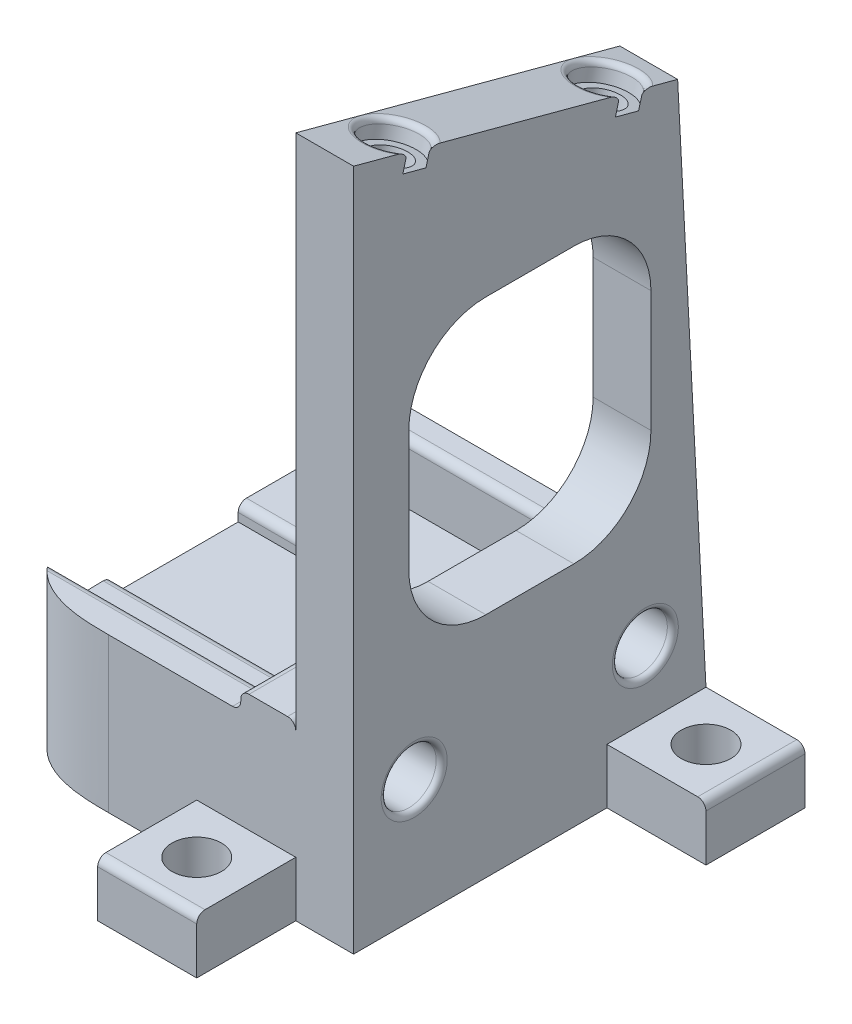
SolidWorks part; units mm, degrees
ref_plane "Front" through (0, 0, 0) normal (0, 0, 1) x (1, 0, 0)
ref_plane "Top" through (0, 0, 0) normal (0, 1, 0) x (1, 0, 0)
ref_plane "Right" through (0, 0, 0) normal (1, 0, 0) x (0, 0, -1)
sketch "Sketch1" plane through (0, 0, 0) normal (1, 0, 0) x (0, 0, -1)
  line L0 (-13.0089, 0) -> (13.0089, 0)
  line L1 (13.0089, 0) -> (13.0089, 8.5)
  line L2 (13.0089, 8.5) -> (5.7589, 8.5)
  line L3 (5.7589, 8.5) -> (5.7589, 7)
  line L4 (5.7589, 7) -> (-5.7589, 7)
  line L5 (-5.7589, 7) -> (-5.7589, 8.5)
  line L6 (-5.7589, 8.5) -> (-13.0089, 8.5)
  line L7 (-13.0089, 8.5) -> (-13.0089, 0)
  dimension "D1" = 8.5
  dimension "D2" = 7.25
  dimension "D3" = 26.0178
  dimension "D4" = 1.5
extrude "Boss-Extrude1" add sketch "Sketch1" along normal mid plane 22
sketch "Sketch3" plane through (0, 0, 0) normal (0, -1, 0) x (1, 0, 0)
  line L1 (-11, -13.0089) -> (11, -13.0089)
  line L2 (-11, -13.0089) -> (-11, -16.0089)
  line L3 (-11, -16.0089) -> (11, -16.0089)
  line L4 (11, -13.0089) -> (11, -16.0089)
  line L5 (-11, 13.0089) -> (11, 13.0089)
  line L6 (-11, 13.0089) -> (-11, 16.0089)
  line L7 (-11, 16.0089) -> (11, 16.0089)
  line L8 (11, 13.0089) -> (11, 16.0089)
  dimension "D1" = 3
  dimension "D2" = 22
  dimension "D3" = 3
  dimension "D4" = 22
extrude "Boss-Extrude2" add sketch "Sketch3" against normal blind 14
sketch "Sketch4" plane through (11, 0, 0) normal (1, 0, 0) x (0, 0, -1)
  line L0 (0, 0) -> (0, 15.7) construction
  line L1 (-16.0089, 0) -> (16.0089, 0) construction
  line L2 (-8.8, 15.7) -> (-16.0089, 15.7)
  line L3 (-16.0089, 14) -> (-16.0089, 0) construction
  line L4 (-16.0089, 15.7) -> (-16.0089, 0)
  line L5 (-16.0089, 0) -> (16.0089, 0)
  line L6 (16.0089, 0) -> (16.0089, 15.7)
  line L7 (16.0089, 14) -> (16.0089, 0) construction
  line L8 (16.0089, 15.7) -> (-8.8, 15.7)
  dimension "D2" = 15.7
extrude "Boss-Extrude3" add sketch "Sketch4" along normal blind 5
sketch "Sketch5" plane through (16, 0, 0) normal (1, 0, 0) x (0, 0, -1)
  line L0 (-16.0089, 11) -> (-10.5, 11) construction
  line L1 (-16.0089, 15.7) -> (-16.0089, 0) construction
  line L2 (-10.5, 11) -> (-10.5, 0) construction
  line L3 (-16.0089, 0) -> (16.0089, 0) construction
  line L4 (0, 0) -> (0, 15.7) construction
  line L5 (16.0089, 15.7) -> (-16.0089, 15.7) construction
  circle A0 centre (-10.5, 11) radius 1.75
  circle A1 centre (10.5, 11) radius 1.75
  dimension "D3" = 3.5
  dimension "D1" = 5.5089
  dimension "D2" = 11
extrude "Cut-Extrude1" cut sketch "Sketch5" against normal through all
sketch "Sketch6" plane through (0, 0, 0) normal (0, -1, 0) x (1, 0, 0)
  line L5 (16, 25.0089) -> (7, 25.0089)
  line L13 (16, 25.0089) -> (16, 16.0089)
  line L14 (16, 16.0089) -> (7, 16.0089)
  line L23 (7, 25.0089) -> (7, 16.0089)
  dimension "D1" = 9
  dimension "D2" = 9
extrude "Boss-Extrude4" add sketch "Sketch6" against normal blind 5
sketch "Sketch10" plane through (0, 0, 0) normal (0, -1, 0) x (1, 0, 0)
  line L7 (11.5, 20.5089) -> (7, 20.5089) construction
  line L8 (7, 25.0089) -> (7, 16.0089) construction
  line L9 (11.5, 20.5089) -> (11.5, 16.0089) construction
  line L10 (16, 16.0089) -> (7, 16.0089) construction
  circle A1 centre (11.5, 20.5089) radius 2.25
  dimension "D1" = 4.5
extrude "Cut-Extrude2" cut sketch "Sketch10" against normal through all
fillet "Fillet1" radius 0.75 11 edges at (0, 8.5, 5.7589) (0, 8.5, -5.7589) (11, 11.25, 13.0089) (11, 11.25, -13.0089) (0, 14, 13.0089) (0, 14, -13.0089) (11, 15.7, 0) (11, 14, 14.5089) (11, 14, -14.5089) (16, 15.7, 0) (11.5, 5, 25.0089)
fillet "Fillet2" radius 10 1 edges at (-11, 7, 16.0089) curvature continuous yes
sketch "Sketch12" plane through (0, 0, 0) normal (0, -1, 0) x (1, 0, 0)
  line L1 (25, -16.0089) -> (16, -16.0089)
  line L2 (25, -16.0089) -> (25, 16.0089)
  line L3 (25, 16.0089) -> (16, 16.0089)
  line L4 (16, -16.0089) -> (16, 16.0089)
  dimension "D1" = 9
extrude "Boss-Extrude5" add sketch "Sketch12" against normal blind 62
sketch "Sketch13" plane through (25, 0, 0) normal (1, 0, 0) x (0, 0, -1)
  line L4 (16.0089, 62) -> (-16.0089, 62)
  line L5 (-16.0089, 62) -> (16.0089, 53.4209)
  line L6 (16.0089, 62) -> (16.0089, 0) construction
  line L7 (16.0089, 53.4209) -> (16.0089, 62)
  dimension "D1" = 15
extrude "Cut-Extrude4" cut sketch "Sketch13" against normal up to surface (9 mm away) up to face at (16, 38.475, 0)
sketch "Sketch14" plane through (25, 0, 0) normal (1, 0, 0) x (0, 0, -1)
  circle A0 centre (-10.5, 11) radius 2.5
  circle A1 centre (10.5, 11) radius 2.5
  dimension "D1" = 5
extrude "Cut-Extrude5" cut sketch "Sketch14" against normal blind 9.75
sketch "Sketch15" plane through (0, 53.8446, -14.4276) normal (0, 0.9659, -0.2588) x (1, 0, 0)
  line L0 (19, 1.6371) -> (19, -5.3629) construction
  line L2 (19, -5.3629) -> (16, -5.3629) construction
  line L3 (16, 0) -> (16, -4.0635) construction
  line L4 (16, 1.6371) -> (25, 1.6371) construction
  line L5 (19, -5.3629) -> (19, -25.3629) construction
  circle A0 centre (19, -5.3629) radius 1.7
  circle A1 centre (19, -25.3629) radius 1.7
  dimension "D4" = 3.4
  dimension "D1" = 3
  dimension "D2" = 7
  dimension "D3" = 20
extrude "Cut-Extrude6" cut sketch "Sketch15" against normal blind 5
sketch "Sketch16" plane through (0, 53.8446, -14.4276) normal (0, 0.9659, -0.2588) x (1, 0, 0)
  circle A0 centre (19, -5.3629) radius 2.5
  circle A1 centre (19, -25.3629) radius 2.5
  dimension "D1" = 5
extrude "Cut-Extrude7" cut sketch "Sketch16" against normal blind 1.6
fillet "Fillet3" radius 0.5 2 edges at (19, 55.8796, -6.8326) (19, 61.056, 12.4859)
fillet "Fillet4" radius 0.5 2 edges at (25, 11, -13) (25, 11, 8)
ref_plane "Plane1" through (0, 62, 0) normal (0, -1, 0) x (-1, 0, 0)
sketch "Sketch17" plane through (0, 62, 0) normal (0, -1, 0) x (-1, 0, 0)
  line L0 (-25, -16.0089) -> (-16, -16.0089) construction
  line L1 (-25, 16.0089) -> (-21.25, 16.0089)
  line L2 (-25, 16.0089) -> (-25, -16.0089)
  line L3 (-25, -16.0089) -> (-21.25, -16.0089)
  line L4 (-21.25, 16.0089) -> (-21.25, -16.0089)
  dimension "D1" = 3.75
extrude "Cut-Extrude9" cut sketch "Sketch17" along normal through all
fillet "Fillet5" radius 0.5 2 edges at (21.25, 11, -13) (21.25, 11, 8)
sketch "Sketch18" plane through (0, 0, 0) normal (0, -1, 0) x (1, 0, 0)
  line L1 (21.25, -16.0089) -> (30.25, -16.0089)
  line L2 (21.25, -16.0089) -> (21.25, -7.0089)
  line L3 (21.25, -7.0089) -> (30.25, -7.0089)
  line L4 (30.25, -16.0089) -> (30.25, -7.0089)
  dimension "D1" = 9
  dimension "D2" = 9
extrude "Boss-Extrude6" add sketch "Sketch18" against normal blind 5
sketch "Sketch19" plane through (0, 5, 0) normal (0, 1, 0) x (1, 0, 0)
  line L0 (21.25, 11.5089) -> (30.25, 11.5089) construction
  line L1 (21.25, 7.0089) -> (21.25, 16.0089) construction
  line L2 (30.25, 16.0089) -> (30.25, 7.0089) construction
  line L3 (25.75, 7.0089) -> (25.75, 16.0089) construction
  line L4 (30.25, 7.0089) -> (21.25, 7.0089) construction
  line L5 (21.25, 16.0089) -> (30.25, 16.0089) construction
  circle A0 centre (25.75, 11.5089) radius 2.25
  dimension "D1" = 4.5
extrude "Cut-Extrude10" cut sketch "Sketch19" against normal up to next
fillet "Fillet6" radius 0.75 1 edges at (30.25, 5, -11.5089)
sketch "Sketch20" plane through (16, 0, 0) normal (-1, 0, 0) x (0, 0, 1)
  line L0 (-11.0089, 45.7) -> (10.9911, 45.7)
  line L1 (10.9911, 45.7) -> (10.9911, 20.7)
  line L2 (10.9911, 20.7) -> (-11.0089, 20.7)
  line L3 (-11.0089, 20.7) -> (-11.0089, 45.7)
  line L4 (-16.0089, 53.4209) -> (-16.0089, 14.95) construction
  line L7 (16.0089, 15.7) -> (-16.0089, 15.7) construction
  point P6 (-16.0089, 34.1854)
  dimension "D1" = 22
  dimension "D2" = 25
  dimension "D3" = 5
  dimension "D4" = 5
extrude "Cut-Extrude11" cut sketch "Sketch20" against normal up to next
sketch "Sketch21" plane through (21.25, 0, 0) normal (1, 0, 0) x (0, 0, -1)
  line L0 (16.0089, 5) -> (16.0089, 53.4209)
  line L1 (16.0089, 53.4209) -> (13.4351, 54.1105)
  line L3 (13.4351, 54.1105) -> (16.0089, 5)
  line L5 (16.0089, 53.4209) -> (11.1641, 54.719) construction
  dimension "D1" = 3
extrude "Cut-Extrude12" cut sketch "Sketch21" against normal through all
fillet "Fillet7" radius 7 4 edges at (18.625, 20.7, -11.0089) (18.625, 20.7, 10.9911) (18.625, 45.7, -11.0089) (18.625, 45.7, 10.9911)
